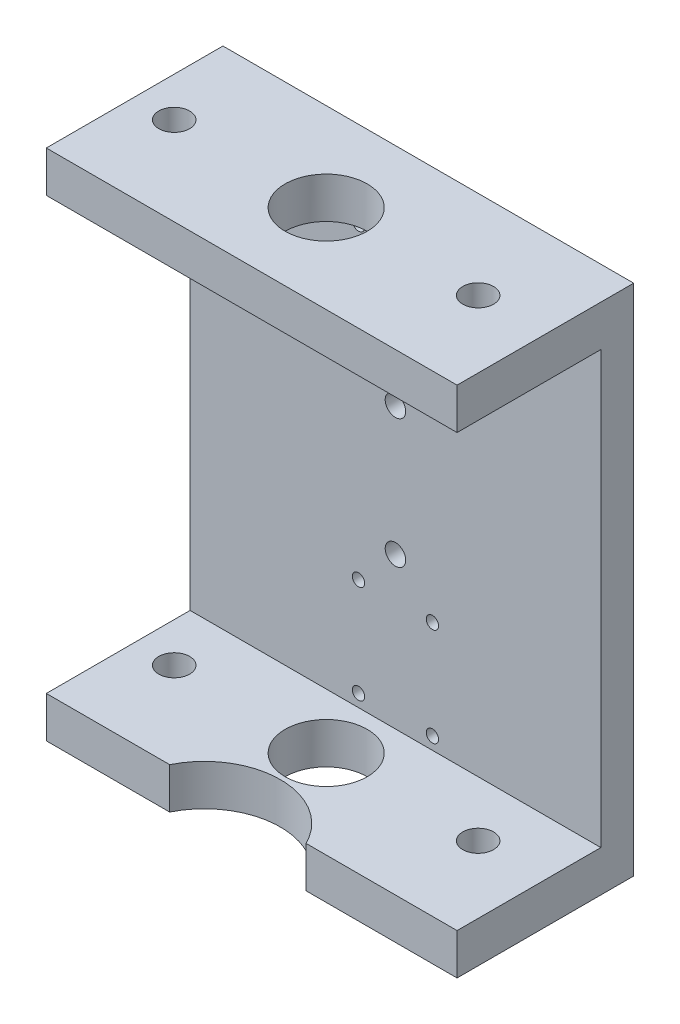
SolidWorks part; units mm, degrees
ref_plane "Front Plane" through (0, 0, 0) normal (0, 0, 1) x (1, 0, 0)
ref_plane "Top Plane" through (0, 0, 0) normal (0, 1, 0) x (1, 0, 0)
ref_plane "Right Plane" through (0, 0, 0) normal (1, 0, 0) x (0, 0, -1)
sketch "Sketch2" plane through (0, 0, 0) normal (0, 0, 1) x (1, 0, 0)
  line L5 (9, -8.0356) -> (-9, -31.9644) construction
  line L6 (-50, 80) -> (50, 80)
  line L7 (-50, 80) -> (-50, -45)
  line L8 (-50, -45) -> (50, -45)
  line L9 (50, 80) -> (50, -45)
  line L10 (-9, -8.0356) -> (9, -31.9644) construction
  line L12 (-9, 66.9644) -> (9, 43.0356) construction
  line L13 (-9, 43.0356) -> (9, 66.9644) construction
  circle A7 centre (-9, -8.0356) radius 1.5
  circle A12 centre (9, -31.9644) radius 1.5
  circle A13 centre (9, -8.0356) radius 1.5
  circle A18 centre (-9, -31.9644) radius 1.5
  circle A27 centre (9, 43.0356) radius 1.5
  circle A28 centre (-9, 43.0356) radius 1.5
  circle A29 centre (-9, 66.9644) radius 1.5
  circle A30 centre (9, 66.9644) radius 1.5
  circle A31 centre (0, 33.18) radius 2.5
  circle A32 centre (0, 1.82) radius 2.5
  point P5 (0, 0)
  point P22 (0, 17.5)
  dimension "D2" = 125
extrude "Boss-Extrude1" add sketch "Sketch2" along normal blind 8
sketch "Sketch5" plane through (0, 0, 8) normal (0, 0, 1) x (1, 0, 0)
  line L8 (-50, 70) -> (-50, 80)
  line L10 (-50, 80) -> (50, 80)
  line L13 (50, -45) -> (50, 80) construction
  line L14 (50, 70) -> (-50, 70)
  line L19 (50, 80) -> (50, 70)
  line L22 (-50, 80) -> (-50, -45) construction
  line L24 (-50, -35) -> (-50, -45)
  line L25 (50, -35) -> (-50, -35)
  line L26 (50, -45) -> (50, -35)
  line L29 (-50, -45) -> (50, -45)
extrude "Boss-Extrude2" add sketch "Sketch5" along normal blind 35
sketch "Sketch7" plane through (0, 80, 0) normal (0, 1, 0) x (1, 0, 0)
  circle A0 centre (-3.365, -21.5) radius 10
  circle A1 centre (-40.365, -21.5) radius 3.75
  circle A2 centre (33.635, -21.5) radius 3.75
  dimension "D1" = 20
  dimension "D4" = 7.5
  dimension "D5" = 7.5
extrude "Cut-Extrude2" cut sketch "Sketch7" against normal blind 290
sketch "Sketch8" plane through (0, -35, 0) normal (0, 1, 0) x (1, 0, 0)
  circle A4 centre (-3.365, -51.1648) radius 18.5
  dimension "D1" = 37
extrude "Cut-Extrude5" cut sketch "Sketch8" against normal through all
